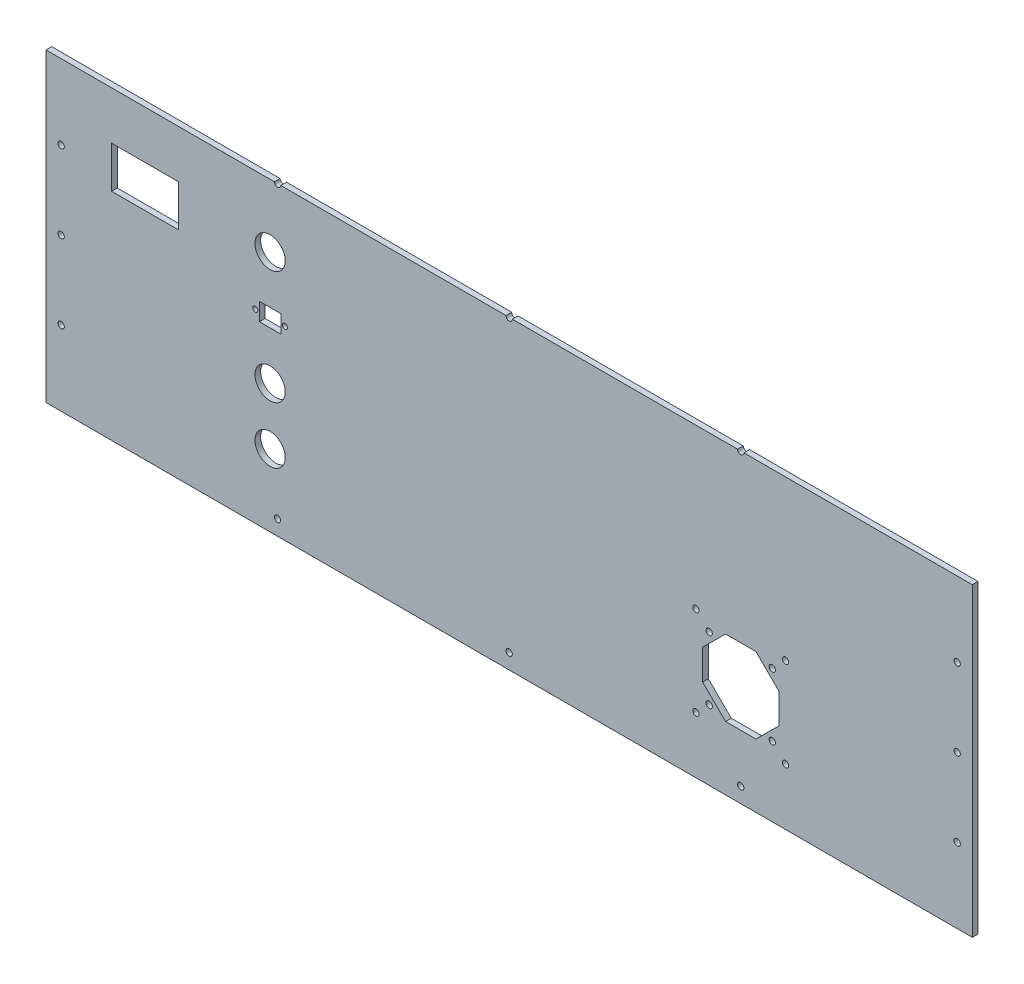
SolidWorks part; units mm, degrees
ref_plane "Front Plane" through (0, 0, 0) normal (0, 0, 1) x (1, 0, 0)
ref_plane "Top Plane" through (0, 0, 0) normal (0, 1, 0) x (1, 0, 0)
ref_plane "Right Plane" through (0, 0, 0) normal (1, 0, 0) x (0, 0, -1)
sketch "Sketch1" plane through (0, 0, 0) normal (0, 0, 1) x (1, 0, 0)
  line L1 (-367, 123.5) -> (-186, 123.5)
  line L2 (-367, 123.5) -> (-367, -118.5)
  line L4 (367, 123.5) -> (367, -118.5)
  line L10 (-367, -118.5) -> (367, -118.5)
  line L11 (0, -118.5) -> (0, 123.5) construction
  line L12 (-181, 123.5) -> (-2.5, 123.5)
  line L13 (2.5, 123.5) -> (181, 123.5)
  line L14 (186, 123.5) -> (367, 123.5)
  line L16 (-367, 2.5) -> (367, 2.5) construction
  arc A3 (-2.5, 123.5) -> (2.5, 123.5) centre (0, 123.5) ccw
  arc A4 (181, 123.5) -> (186, 123.5) centre (183.5, 123.5) ccw
  arc A5 (-186, 123.5) -> (-181, 123.5) centre (-183.5, 123.5) ccw
  circle A7 centre (-355, 2.5) radius 2.5
  circle A8 centre (-355, 64.25) radius 2.5
  circle A9 centre (-355, -59.25) radius 2.5
  circle A10 centre (355, -59.25) radius 2.5
  circle A11 centre (355, 2.5) radius 2.5
  circle A12 centre (355, 64.25) radius 2.5
  circle A14 centre (-183.5, -106.5) radius 2.5
  circle A15 centre (0, -106.5) radius 2.5
  circle A16 centre (183.5, -106.5) radius 2.5
  point P18 (-367, 123.5)
  point P32 (0, 0)
  point P33 (0, 0)
  dimension "D5" = 2
  dimension "D3" = 5
  dimension "D7" = 12
  dimension "D10" = 12
  dimension "D11" = 183.5
  dimension "D1" = 242
  dimension "D2" = 734
  dimension "D4" = 367
  dimension "D13" = 12
  dimension "D14" = 12
  dimension "D6" = 2
  dimension "D8" = 2
  dimension "D9" = 2
  dimension "D12" = 3
extrude "Boss-Extrude1" add sketch "Sketch1" along normal blind 4.5
sketch "Sketch2" plane through (0, 0, 4.5) normal (0, 0, 1) x (1, 0, 0)
  line L0 (-189.4251, 85.5) -> (-367, 85.5)
  line L1 (-315, 85.5) -> (-262, 85.5)
  line L2 (-315, 85.5) -> (-315, 52.5)
  line L3 (-315, 52.5) -> (-262, 52.5)
  line L4 (-262, 85.5) -> (-262, 52.5)
  line L5 (-367, 123.5) -> (-367, -118.5) construction
  line L6 (-186, 123.5) -> (-367, 123.5) construction
  line L7 (-189.4251, 73.5) -> (-189.4251, 28.5) construction
  line L8 (183.5, 121) -> (183.5, -118.5) construction
  line L9 (-367, -118.5) -> (367, -118.5) construction
  line L10 (171.5, -8.1179) -> (195.5, -8.1179)
  line L11 (171.5, -68.1179) -> (195.5, -68.1179)
  line L12 (153.3069, -26.1179) -> (153.3069, -50.1179)
  line L13 (247.4435, -38.1179) -> (106.5361, -38.1179) construction
  line L14 (171.5, -8.1179) -> (153.3069, -26.1179)
  line L15 (153.3069, -50.1179) -> (171.5, -68.1179)
  line L16 (213.6931, -50.1179) -> (195.5, -68.1179)
  line L17 (213.6931, -26.1179) -> (213.6931, -50.1179)
  line L18 (195.5, -8.1179) -> (213.6931, -26.1179)
  line L20 (-197.9251, 35.5) -> (-180.9251, 35.5)
  line L21 (-197.9251, 35.5) -> (-197.9251, 21.5)
  line L22 (-197.9251, 21.5) -> (-180.9251, 21.5)
  line L23 (-180.9251, 35.5) -> (-180.9251, 21.5)
  circle A0 centre (-189.4251, 73.5) radius 12
  circle A7 centre (-189.4251, -16.5) radius 12
  circle A8 centre (-189.4251, -61.5) radius 12
  arc A9 (181, 123.5) -> (186, 123.5) centre (183.5, 123.5) ccw construction
  circle A10 centre (-355, 64.25) radius 2.5 construction
  circle A12 centre (208.5, -13.1179) radius 2.5
  circle A13 centre (208.5, -63.1179) radius 2.5
  circle A14 centre (158.5, -63.1179) radius 2.5
  circle A15 centre (158.5, -13.1179) radius 2.5
  circle A16 centre (219, -2.6179) radius 2.5
  circle A17 centre (219, -73.6179) radius 2.5
  circle A18 centre (148, -2.6179) radius 2.5
  circle A19 centre (148, -73.6179) radius 2.5
  circle A20 centre (-189.4251, 28.5) radius 12 [skipped]
  circle A21 centre (-201.1851, 28.5) radius 2
  circle A22 centre (-177.6651, 28.5) radius 2
  point P45 (183.5, -68.1179)
  point P50 (183.5, -8.1179)
  dimension "D5" = 45
  dimension "D7" = 0
  dimension "D3" = 50
  dimension "D6" = 40
  dimension "D8" = 25
  dimension "D9" = 25
  dimension "D19" = 71
  dimension "D21" = 24
  dimension "D1" = 53
  dimension "D2" = 33
  dimension "D4" = 4
  dimension "D10" = 50
  dimension "D11" = 60
  dimension "D12" = 5
  dimension "D13" = 12
  dimension "D14" = 12
  dimension "D15" = 24
  dimension "D16" = 25
  dimension "D17" = 12
  dimension "D18" = 35.5
  dimension "D20" = 35.5
  dimension "D22" = 7
  dimension "D23" = 8.5
  dimension "D24" = 14
  dimension "D25" = 17
extrude "Cut-Extrude2" cut sketch "Sketch2" against normal blind 10 contours L4 L0 L2 L3 | A0 | A7 | A8 | L18 L10 L14 L12 L15 L11 L16 L17 | A15 | A12 | A13 | A14 | A18 | A16 | A19 | A17 region at (-288.5, 69, 4.5) region at (-189.4251, 73.5, 4.5) region at (183.5, -38.1179, 4.5) region at (-189.4251, -16.5, 4.5) region at (-189.4251, -61.5, 4.5)
sketch "Sketch4" plane through (0, 0, 4.5) normal (0, 0, 1) x (1, 0, 0)
  line L0 (-229.4251, 53.5) -> (-149.4251, 53.5) construction
  line L1 (-229.4251, 8.5517) -> (-149.4251, 8.5517) construction
  line L2 (-229.4251, -36.3967) -> (-149.4251, -36.3967) construction
  line L3 (-229.4251, -81.345) -> (-149.4251, -81.345) construction
  line L4 (-189.4251, 73.5) -> (-189.4251, 28.5) construction
  text T0 "SMOOTHIE\r\n" font "Century Gothic" height in points 26
  text T1 "SMOOTHIE ENET" font "Century Gothic" height in points 26
  text T2 "DUE\r\n" font "Century Gothic" height in points 26
  text T3 "DUE SERIAL 1" font "Century Gothic" height in points 26
  dimension "D1" = 20
  dimension "D2" = 40
  dimension "D3" = 80
  dimension "D4" = 4
extrude "Cut-Extrude3" cut sketch "Sketch2<6>" against normal blind 10 contours L20 L23 L22 L21 | A21 | A22
sketch "Sketch2<6>" plane through (0, 0, 4.5) normal (0, 0, 1) x (1, 0, 0) same geometry as "Sketch2"
